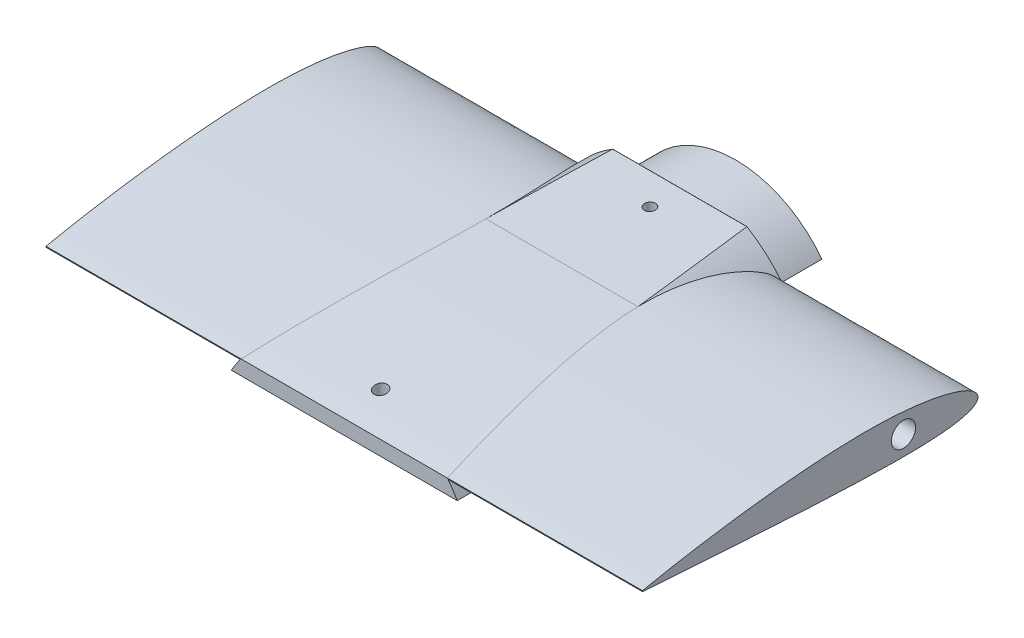
SolidWorks part; units mm, degrees
ref_plane "Front Plane" through (0, 0, 0) normal (0, 0, 1) x (1, 0, 0)
ref_plane "Top Plane" through (0, 0, 0) normal (0, 1, 0) x (1, 0, 0)
ref_plane "Right Plane" through (0, 0, 0) normal (1, 0, 0) x (0, 0, -1)
sketch "Sketch4" plane through (0, 0, 0) normal (0, 0, 1) x (1, 0, 0)
  line L0 (-30.3109, 17.5) -> (30.3109, 17.5)
  arc A1 (30.3109, 17.5) -> (-30.3109, 17.5) centre (0, 0) ccw
  dimension "D1" = 35
  dimension "D2" = 17.5
extrude "Exterior" add sketch "Sketch4" along normal blind 90 contours L0 A1
sketch "Sketch5" plane through (0, 0, 0) normal (0, 0, -1) x (-1, 0, 0)
  line L0 (30.3109, 17.5) -> (-30.3109, 17.5) construction
  line L1 (23.1247, 17.5) -> (-23.1247, 17.5)
  arc A0 (23.1247, 17.5) -> (-23.1247, 17.5) centre (0, 0) ccw
  dimension "D1" = 58
extrude "Boss-Extrude1" add sketch "Sketch5" along normal blind 15
curve "Curve3"
  spline degree 3 poles (0, 1.3, 1000) (0, 4.7133, 983.3426) (0, 11.531, 950.0715) (0, 24.0186, 883.4722) (0, 37.8548, 800.1781) (0, 52.175, 700.1592) (0, 64.1175, 600.1567) (0, 72.8619, 500.1109) (0, 78.7837, 400.0878) (0, 79.786, 316.6355) (0, 77.0249, 249.9395) (0, 72.979, 199.8766) (0, 66.5721, 149.7505) (0, 58.6825, 108.0331) (0, 49.7566, 74.7751) (0, 41.6416, 49.5609) (0, 32.1864, 28.1982) (0, 20.723, 9.771) (0, 0.8988, -6.2982) (0, -16.5264, 10.3934) (0, -24.4739, 28.476) (0, -30.5108, 49.7447) (0, -34.8393, 74.8759) (0, -38.5332, 108.2669) (0, -41.3764, 149.947) (0, -42.5163, 199.9941) (0, -42.3574, 250.0055) (0, -40.8857, 316.6783) (0, -38.2375, 400.0272) (0, -33.6287, 500.0334) (0, -27.6385, 600.0106) (0, -21.4122, 700.0048) (0, -15.1098, 800.0161) (0, -9.3053, 883.3314) (0, -4.8282, 950.0042) (0, -2.4761, 983.334) (0, -1.3, 1000) knots 0 0 0 0 0.025012 0.049959 0.099673 0.149206 0.198581 0.247805 0.296917 0.345953 0.370492 0.395091 0.419815 0.444799 0.45749 0.470406 0.483879 0.491264 0.503459 0.513609 0.520451 0.533235 0.545691 0.558032 0.582609 0.607135 0.631652 0.656174 0.705234 0.75432 0.803437 0.852566 0.901701 0.950849 0.975423 1 1 1 1
sketch "Sketch7" plane through (0, 0, 0) normal (1, 0, 0) x (0, 0, -1)
  line L0 (-90, 21.4324) -> (-90, 21.1984)
  line L1 (-90, 21.3154) -> (0, 21.434) construction
  line L2 (0, 21.434) -> (-0.0572, 64.8516) construction
  line L7 (-90, 17.5) -> (0, 17.5) construction
  line L9 (0, 17.5) -> (0, 29) construction
  spline S1 degree 3 poles (-90, 21.4324) (-88.5009, 21.7395) (-85.5067, 22.3531) (-79.5132, 23.4769) (-72.0173, 24.7221) (-63.0162, 26.0108) (-54.0165, 27.0856) (-45.013, 27.8725) (-36.0116, 28.4054) (-28.5014, 28.4956) (-22.4991, 28.2471) (-17.9938, 27.883) (-13.4827, 27.3065) (-9.7284, 26.5964) (-6.7354, 25.7932) (-4.4663, 25.0629) (-2.5438, 24.212) (-0.8854, 23.1803) (0.5607, 21.3963) (-0.9415, 19.8281) (-2.5688, 19.1129) (-4.4828, 18.5696) (-6.7445, 18.18) (-9.7495, 17.8476) (-13.5004, 17.5918) (-18.0044, 17.4892) (-22.5051, 17.5035) (-28.5052, 17.6359) (-36.0061, 17.8742) (-45.0061, 18.289) (-54.0034, 18.8281) (-63.0023, 19.3884) (-72.0027, 19.9556) (-79.5005, 20.478) (-85.5007, 20.8809) (-88.5002, 21.0925) (-90, 21.1984) knots 0 0 0 0 0.025012 0.049959 0.099673 0.149206 0.198581 0.247805 0.296917 0.345953 0.370492 0.395091 0.419815 0.444799 0.45749 0.470406 0.483879 0.491264 0.503459 0.513609 0.520451 0.533235 0.545691 0.558032 0.582609 0.607135 0.631652 0.656174 0.705234 0.75432 0.803437 0.852566 0.901701 0.950849 0.975423 1 1 1 1
  dimension "D1" = 90
ref_plane "Plane1" through (80, 0, 0) normal (1, 0, 0) x (0, 0, -1)
ref_plane "Plane2" through (-80, 0, 0) normal (1, 0, 0) x (0, 0, -1)
sketch "Sketch8" plane through (80, 0, 0) normal (1, 0, 0) x (0, 0, -1)
  line L0 (-90, 21.4324) -> (-90, 21.1984)
  spline S0 degree 3 poles (-471.7106, 945.6993) (-211.2582, -27.034) (-149.3449, 10.3833) (-79.5132, 23.4769) (-72.0173, 24.7221) (-63.0162, 26.0108) (-54.0165, 27.0856) (-45.013, 27.8725) (-36.0116, 28.4054) (-28.5014, 28.4956) (-22.4991, 28.2471) (-17.9938, 27.883) (-13.4827, 27.3065) (-9.7284, 26.5964) (-6.7354, 25.7932) (-4.4663, 25.0629) (-2.5438, 24.212) (-0.8854, 23.1803) (0.5607, 21.3963) (-0.9415, 19.8281) (-2.5688, 19.1129) (-4.4828, 18.5696) (-6.7445, 18.18) (-9.7495, 17.8476) (-13.5004, 17.5918) (-18.0044, 17.4892) (-22.5051, 17.5035) (-28.5052, 17.6359) (-36.0061, 17.8742) (-45.0061, 18.289) (-54.0034, 18.8281) (-63.0023, 19.3884) (-72.0027, 19.9556) (-79.5005, 20.478) (-193.1952, 28.1126) (-302.9336, 49.4451) (-477.9813, -900.4458) knots -1.061635 -1.061635 -1.061635 -1.061635 0.025012 0.049959 0.099673 0.149206 0.198581 0.247805 0.296917 0.345953 0.370492 0.395091 0.419815 0.444799 0.45749 0.470406 0.483879 0.491264 0.503459 0.513609 0.520451 0.533235 0.545691 0.558032 0.582609 0.607135 0.631652 0.656174 0.705234 0.75432 0.803437 0.852566 0.901701 0.950849 0.975423 2.764334 2.764334 2.764334 2.764334 only from (-90, 21.4324) to (-90, 21.1984) construction
  spline S1 degree 3 poles (-90, 21.4324) (-88.5009, 21.7395) (-85.5067, 22.3531) (-79.5132, 23.4769) (-72.0173, 24.7221) (-63.0162, 26.0108) (-54.0165, 27.0856) (-45.013, 27.8725) (-36.0116, 28.4054) (-28.5014, 28.4956) (-22.4991, 28.2471) (-17.9938, 27.883) (-13.4827, 27.3065) (-9.7284, 26.5964) (-6.7354, 25.7932) (-4.4663, 25.0629) (-2.5438, 24.212) (-0.8854, 23.1803) (0.5607, 21.3963) (-0.9415, 19.8281) (-2.5688, 19.1129) (-4.4828, 18.5696) (-6.7445, 18.18) (-9.7495, 17.8476) (-13.5004, 17.5918) (-18.0044, 17.4892) (-22.5051, 17.5035) (-28.5052, 17.6359) (-36.0061, 17.8742) (-45.0061, 18.289) (-54.0034, 18.8281) (-63.0023, 19.3884) (-72.0027, 19.9556) (-79.5005, 20.478) (-85.5007, 20.8809) (-88.5002, 21.0925) (-90, 21.1984) knots 0 0 0 0 0.025012 0.049959 0.099673 0.149206 0.198581 0.247805 0.296917 0.345953 0.370492 0.395091 0.419815 0.444799 0.45749 0.470406 0.483879 0.491264 0.503459 0.513609 0.520451 0.533235 0.545691 0.558032 0.582609 0.607135 0.631652 0.656174 0.705234 0.75432 0.803437 0.852566 0.901701 0.950849 0.975423 1 1 1 1
sketch "Sketch9" plane through (-80, 0, 0) normal (1, 0, 0) x (0, 0, -1)
  line L0 (-90, 21.4324) -> (-90, 21.1984)
  spline S0 degree 3 poles (-471.7106, 945.6993) (-211.2582, -27.034) (-149.3449, 10.3833) (-79.5132, 23.4769) (-72.0173, 24.7221) (-63.0162, 26.0108) (-54.0165, 27.0856) (-45.013, 27.8725) (-36.0116, 28.4054) (-28.5014, 28.4956) (-22.4991, 28.2471) (-17.9938, 27.883) (-13.4827, 27.3065) (-9.7284, 26.5964) (-6.7354, 25.7932) (-4.4663, 25.0629) (-2.5438, 24.212) (-0.8854, 23.1803) (0.5607, 21.3963) (-0.9415, 19.8281) (-2.5688, 19.1129) (-4.4828, 18.5696) (-6.7445, 18.18) (-9.7495, 17.8476) (-13.5004, 17.5918) (-18.0044, 17.4892) (-22.5051, 17.5035) (-28.5052, 17.6359) (-36.0061, 17.8742) (-45.0061, 18.289) (-54.0034, 18.8281) (-63.0023, 19.3884) (-72.0027, 19.9556) (-79.5005, 20.478) (-193.1952, 28.1126) (-302.9336, 49.4451) (-477.9813, -900.4458) knots -1.061635 -1.061635 -1.061635 -1.061635 0.025012 0.049959 0.099673 0.149206 0.198581 0.247805 0.296917 0.345953 0.370492 0.395091 0.419815 0.444799 0.45749 0.470406 0.483879 0.491264 0.503459 0.513609 0.520451 0.533235 0.545691 0.558032 0.582609 0.607135 0.631652 0.656174 0.705234 0.75432 0.803437 0.852566 0.901701 0.950849 0.975423 2.764334 2.764334 2.764334 2.764334 only from (-90, 21.4324) to (-90, 21.1984) construction
  spline S1 degree 3 poles (-90, 21.4324) (-88.5009, 21.7395) (-85.5067, 22.3531) (-79.5132, 23.4769) (-72.0173, 24.7221) (-63.0162, 26.0108) (-54.0165, 27.0856) (-45.013, 27.8725) (-36.0116, 28.4054) (-28.5014, 28.4956) (-22.4991, 28.2471) (-17.9938, 27.883) (-13.4827, 27.3065) (-9.7284, 26.5964) (-6.7354, 25.7932) (-4.4663, 25.0629) (-2.5438, 24.212) (-0.8854, 23.1803) (0.5607, 21.3963) (-0.9415, 19.8281) (-2.5688, 19.1129) (-4.4828, 18.5696) (-6.7445, 18.18) (-9.7495, 17.8476) (-13.5004, 17.5918) (-18.0044, 17.4892) (-22.5051, 17.5035) (-28.5052, 17.6359) (-36.0061, 17.8742) (-45.0061, 18.289) (-54.0034, 18.8281) (-63.0023, 19.3884) (-72.0027, 19.9556) (-79.5005, 20.478) (-85.5007, 20.8809) (-88.5002, 21.0925) (-90, 21.1984) knots 0 0 0 0 0.025012 0.049959 0.099673 0.149206 0.198581 0.247805 0.296917 0.345953 0.370492 0.395091 0.419815 0.444799 0.45749 0.470406 0.483879 0.491264 0.503459 0.513609 0.520451 0.533235 0.545691 0.558032 0.582609 0.607135 0.631652 0.656174 0.705234 0.75432 0.803437 0.852566 0.901701 0.950849 0.975423 1 1 1 1
loft "Loft9" add profiles "Sketch8", "Sketch9" connector at (80, 21.4324, 90) connector at (-80, 21.4324, 90)
sketch "Sketch12" plane through (80, 0, 0) normal (1, 0, 0) x (0, 0, -1)
  line L0 (-90, 21.4324) -> (-90, 21.1984) construction
  line L1 (-90, 21.4324) -> (-90, 21.1984)
  line L2 (-90, 21.4324) -> (-97.2409, 26.9065)
  line L3 (-97.2409, 26.9065) -> (-90.2923, 42.7722)
  line L4 (-90.2923, 42.7722) -> (-30.1138, 44.0233)
  line L5 (-30.1138, 44.0233) -> (6.4186, 38.5184)
  line L6 (6.4186, 38.5184) -> (-0.0113, 30.0134)
  line L7 (0, 21.434) -> (-0.0572, 64.8516) construction
  line L8 (-0.0113, 30.0134) -> (-31.6288, 28.4362)
  spline S0 degree 3 poles (-471.7106, 945.6993) (-211.2582, -27.034) (-149.3449, 10.3833) (-79.5132, 23.4769) (-72.0173, 24.7221) (-63.0162, 26.0108) (-54.0165, 27.0856) (-45.013, 27.8725) (-36.0116, 28.4054) (-28.5014, 28.4956) (-22.4991, 28.2471) (-17.9938, 27.883) (-13.4827, 27.3065) (-9.7284, 26.5964) (-6.7354, 25.7932) (-4.4663, 25.0629) (-2.5438, 24.212) (-0.8854, 23.1803) (0.5607, 21.3963) (-0.9415, 19.8281) (-2.5688, 19.1129) (-4.4828, 18.5696) (-6.7445, 18.18) (-9.7495, 17.8476) (-13.5004, 17.5918) (-18.0044, 17.4892) (-22.5051, 17.5035) (-28.5052, 17.6359) (-36.0061, 17.8742) (-45.0061, 18.289) (-54.0034, 18.8281) (-63.0023, 19.3884) (-72.0027, 19.9556) (-79.5005, 20.478) (-193.1952, 28.1126) (-302.9336, 49.4451) (-477.9813, -900.4458) knots -1.061635 -1.061635 -1.061635 -1.061635 0.025012 0.049959 0.099673 0.149206 0.198581 0.247805 0.296917 0.345953 0.370492 0.395091 0.419815 0.444799 0.45749 0.470406 0.483879 0.491264 0.503459 0.513609 0.520451 0.533235 0.545691 0.558032 0.582609 0.607135 0.631652 0.656174 0.705234 0.75432 0.803437 0.852566 0.901701 0.950849 0.975423 2.764334 2.764334 2.764334 2.764334 only from (-90, 21.4324) to (-90, 21.1984) construction
  spline S1 degree 3 poles (-90, 21.4324) (-88.5009, 21.7395) (-85.5067, 22.3531) (-79.5132, 23.4769) (-72.0173, 24.7221) (-63.0162, 26.0108) (-54.0165, 27.0856) (-45.013, 27.8725) (-37.5506, 28.3143) (-33.0875, 28.4219) (-31.6288, 28.4362) knots 0 0 0 0 0.025012 0.049959 0.099673 0.149206 0.198581 0.247805 0.296917 0.320756 0.320756 0.320756 0.320756
  spline S2 degree 3 poles (-90, 21.4324) (-88.518, 21.738) (-85.5578, 22.3484) (-79.6323, 23.4671) (-72.2211, 24.7077) (-63.3216, 25.9932) (-54.4234, 27.0671) (-45.5209, 27.8564) (-37.9232, 28.3157) (-33.2903, 28.4252) (-31.6288, 28.4362) knots 0 0 0 0 0.025012 0.049959 0.099673 0.149206 0.198581 0.247805 0.296917 0.324377 0.324377 0.324377 0.324377
extrude "Cut-Extrude1" cut sketch "Sketch12" against normal through all
sketch "Sketch13" plane through (-80, 0, 0) normal (-1, 0, 0) x (0, 0, 1)
  line L0 (20, 17.5001) -> (20, 28.0366) construction
  circle A0 centre (20, 22.7683) radius 3.25
  spline S0 degree 3 poles (90, 21.4324) (88.5009, 21.7395) (85.5067, 22.3531) (79.5132, 23.4769) (72.0173, 24.7221) (63.0162, 26.0108) (54.0165, 27.0856) (45.013, 27.8725) (36.0116, 28.4054) (28.5014, 28.4956) (22.4991, 28.2471) (17.9938, 27.883) (13.4827, 27.3065) (9.7284, 26.5964) (6.7354, 25.7932) (4.4663, 25.0629) (2.5438, 24.212) (0.8854, 23.1803) (-0.5607, 21.3963) (0.9415, 19.8281) (2.5688, 19.1129) (4.4828, 18.5696) (6.7445, 18.18) (9.7495, 17.8476) (13.5004, 17.5918) (18.0044, 17.4892) (22.5051, 17.5035) (28.5052, 17.6359) (36.0061, 17.8742) (45.0061, 18.289) (54.0034, 18.8281) (63.0023, 19.3884) (72.0027, 19.9556) (79.5005, 20.478) (85.5007, 20.8809) (88.5002, 21.0925) (90, 21.1984) knots 0 0 0 0 0.025012 0.049959 0.099673 0.149206 0.198581 0.247805 0.296917 0.345953 0.370492 0.395091 0.419815 0.444799 0.45749 0.470406 0.483879 0.491264 0.503459 0.513609 0.520451 0.533235 0.545691 0.558032 0.582609 0.607135 0.631652 0.656174 0.705234 0.75432 0.803437 0.852566 0.901701 0.950849 0.975423 1 1 1 1 construction
  point P8 (20, 22.7683)
  dimension "D1" = 6.5
  dimension "D2" = 20
extrude "Cut-Extrude2" cut sketch "Sketch13" against normal up to surface (160 mm away) up to face at (80, 23.689, 70.5429)
ref_plane "Plane3" through (0, 30, 0) normal (0, 1, 0) x (1, 0, 0)
ref_plane "Plane4" through (0, 30, 0) normal (0, 1, 0) x (1, 0, 0)
sketch "Sketch15" plane through (0, 30, 0) normal (0, 1, 0) x (1, 0, 0)
  line L0 (0, -90) -> (0, 0) construction
  line L1 (-18.0055, -0.0113) -> (18.0055, -0.0113) construction
  circle A0 centre (0, -8.0113) radius 1.5
  dimension "D1" = 3
  dimension "D2" = 8
extrude "Cut-Extrude3" cut sketch "Sketch15" against normal through all
sketch "Sketch16" plane through (0, 30, 0) normal (0, 1, 0) x (1, 0, 0)
  line L0 (0, -9.0116) -> (0, 9.0116) construction
  circle A0 centre (0, -80.2283) radius 1.75
  dimension "D1" = 3.5
extrude "Cut-Extrude4" cut sketch "Sketch16" against normal through all
equation "\"fuse_diam\"= 0.07"
equation "\"fuse_rad\"= 0.035"
equation "\"battery_length\"= 0.076"
equation "\"battery_width\"= 0.034"
equation "\"battery_height\"= 0.051"
equation "\"bat_bay_length\"= 0.096"
equation "\"shell\"= 0.002"
equation "\"D1@Exterior\"=\"chord_length\""
equation "\"wing_shelf\"= 0.0175"
equation "\"chord_length\"= 0.09"
equation "\"tail_length\"= 0.26598000000000005"
equation "\"tail_diam\"= 0.035"
equation "\"connector\"= 0.06649500000000001"
equation "\"D2@Sketch4\"=\"wing_shelf\""
equation "\"D1@Sketch4\"=\"fuse_rad\""
equation "\"D1@Sketch5\"=\"fuse_diam\"-0.012"
equation "\"D1@Sketch7\"=\"chord_length\""
